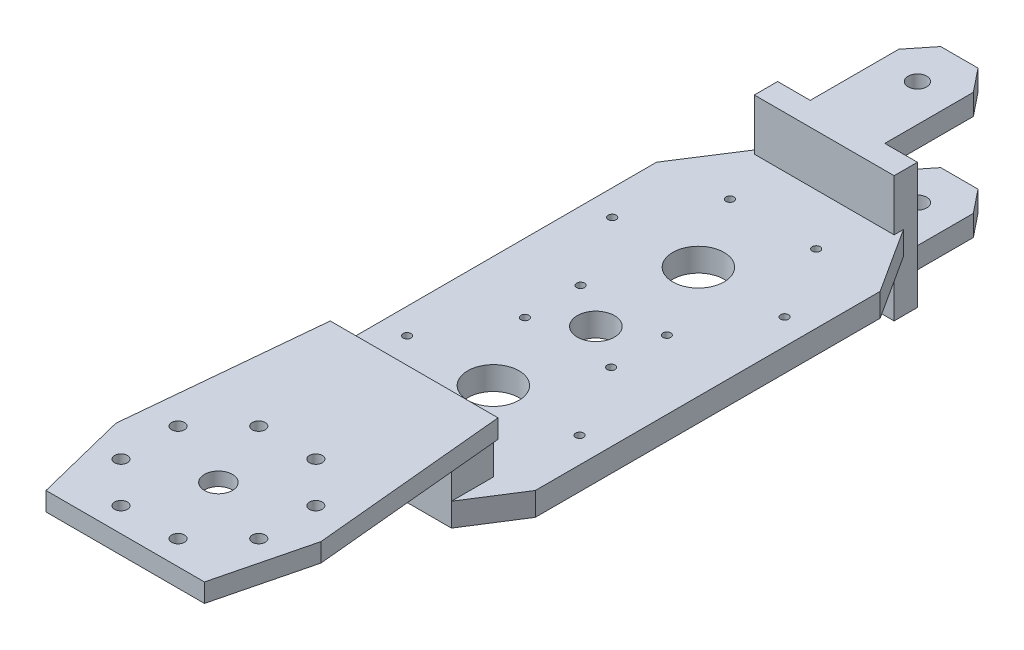
SolidWorks part; units mm, degrees
ref_plane "Front Plane" through (0, 0, 0) normal (0, 0, 1) x (1, 0, 0)
ref_plane "Top Plane" through (0, 0, 0) normal (0, 1, 0) x (1, 0, 0)
ref_plane "Right Plane" through (0, 0, 0) normal (1, 0, 0) x (0, 0, -1)
ref_plane "PL_Knee_Plate_base" through (0, 20, 0) normal (0, 1, 0) x (1, 0, 0)
sketch "SK_Knee_Plate" plane through (0, 20, 0) normal (0, 1, 0) x (1, 0, 0)
  line L0 (-34, -40) -> (34, -40)
  line L1 (34, -40) -> (44, 0)
  line L2 (44, 0) -> (36, 84)
  line L3 (36, 84) -> (-36, 84)
  line L4 (-36, 84) -> (-44, 0)
  line L5 (-44, 0) -> (-34, -40)
  circle A0 centre (29.5641, 12.2459) radius 2.75
  circle A1 centre (12.2459, 29.5641) radius 2.75
  circle A2 centre (-12.2459, 29.5641) radius 2.75
  circle A3 centre (-29.5641, 12.2459) radius 2.75
  circle A4 centre (-29.5641, -12.2459) radius 2.75
  circle A5 centre (-12.2459, -29.5641) radius 2.75
  circle A6 centre (12.2459, -29.5641) radius 2.75
  circle A7 centre (29.5641, -12.2459) radius 2.75
  circle A8 centre (0, 0) radius 6
  dimension "D11_SK_Knee_Plate" = 5.5
  dimension "D14_SK_Knee_Plate" = 5.5
  dimension "D17_SK_Knee_Plate" = 5.5
  dimension "D20_SK_Knee_Plate" = 5.5
  dimension "D23_SK_Knee_Plate" = 5.5
  dimension "D26_SK_Knee_Plate" = 5.5
  dimension "D29_SK_Knee_Plate" = 5.5
  dimension "D32_SK_Knee_Plate" = 5.5
  dimension "D35_SK_Knee_Plate" = 12
  dimension "P1" = 34
  dimension "P2" = 40
  dimension "P3" = 34
  dimension "P4" = 40
  dimension "P5" = 44
  dimension "P6" = 36
  dimension "P7" = 84
  dimension "P8" = 36
  dimension "P9" = 84
  dimension "P10" = 44
  dimension "P12" = 29.5641
  dimension "P13" = 12.2459
  dimension "P15" = 12.2459
  dimension "P16" = 29.5641
  dimension "P18" = 12.2459
  dimension "P19" = 29.5641
  dimension "P21" = 29.5641
  dimension "P22" = 12.2459
  dimension "P24" = 29.5641
  dimension "P25" = 12.2459
  dimension "P27" = 12.2459
  dimension "P28" = 29.5641
  dimension "P30" = 12.2459
  dimension "P31" = 29.5641
  dimension "P33" = 29.5641
  dimension "P34" = 12.2459
extrude "Knee_Plate" add sketch "SK_Knee_Plate" along normal blind 8
ref_plane "PL_Knee_Pilot_Recess_base" through (0, 20, 0) normal (0, 1, 0) x (1, 0, 0)
sketch "SK_Knee_Pilot_Recess" plane through (0, 20, 0) normal (0, 1, 0) x (1, 0, 0)
  circle A0 centre (0, 0) radius 25.15
  dimension "D1_SK_Knee_Pilot_Recess" = 50.3
extrude "Knee_Pilot_Recess" cut sketch "SK_Knee_Pilot_Recess" along normal blind 2.2
ref_plane "PL_Joggle_base" through (0, 0, -84) normal (0, 0, 1) x (1, 0, 0)
sketch "SK_Joggle" plane through (0, 0, -84) normal (0, 0, 1) x (1, 0, 0)
  line L0 (-34, 28) -> (34, 28)
  line L1 (34, 28) -> (34, -5)
  line L2 (34, -5) -> (-34, -5)
  line L3 (-34, -5) -> (-34, 28)
  dimension "P1" = 34
  dimension "P2" = 28
  dimension "P3" = 34
  dimension "P4" = 28
  dimension "P5" = 34
  dimension "P6" = 5
  dimension "P7" = 34
  dimension "P8" = 5
extrude "Joggle" add sketch "SK_Joggle" along normal blind 18
ref_plane "PL_Web_base" through (0, -5, 0) normal (0, 1, 0) x (1, 0, 0)
sketch "SK_Web" plane through (0, -5, 0) normal (0, 1, 0) x (1, 0, 0)
  line L0 (-34, 66) -> (34, 66)
  line L1 (34, 66) -> (48, 88)
  line L2 (48, 88) -> (48, 236)
  line L3 (48, 236) -> (30, 264)
  line L4 (30, 264) -> (-30, 264)
  line L5 (-30, 264) -> (-48, 236)
  line L6 (-48, 236) -> (-48, 88)
  line L7 (-48, 88) -> (-34, 66)
  circle A0 centre (37, 118) radius 1.7
  circle A1 centre (18.5, 150.0429) radius 1.7
  circle A2 centre (-18.5, 150.0429) radius 1.7
  circle A3 centre (-37, 118) radius 1.7
  circle A4 centre (-18.5, 85.9571) radius 1.7
  circle A5 centre (18.5, 85.9571) radius 1.7
  circle A6 centre (37, 206) radius 1.7
  circle A7 centre (18.5, 238.0429) radius 1.7
  circle A8 centre (-18.5, 238.0429) radius 1.7
  circle A9 centre (-37, 206) radius 1.7
  circle A10 centre (-18.5, 173.9571) radius 1.7
  circle A11 centre (18.5, 173.9571) radius 1.7
  circle A12 centre (0, 118) radius 11
  circle A13 centre (0, 206) radius 11
  circle A14 centre (0, 162) radius 8
  dimension "D17_SK_Web" = 3.4
  dimension "D20_SK_Web" = 3.4
  dimension "D23_SK_Web" = 3.4
  dimension "D26_SK_Web" = 3.4
  dimension "D29_SK_Web" = 3.4
  dimension "D32_SK_Web" = 3.4
  dimension "D35_SK_Web" = 3.4
  dimension "D38_SK_Web" = 3.4
  dimension "D41_SK_Web" = 3.4
  dimension "D44_SK_Web" = 3.4
  dimension "D47_SK_Web" = 3.4
  dimension "D50_SK_Web" = 3.4
  dimension "D53_SK_Web" = 22
  dimension "D55_SK_Web" = 22
  dimension "D57_SK_Web" = 16
  dimension "P1" = 34
  dimension "P2" = 66
  dimension "P3" = 34
  dimension "P4" = 66
  dimension "P5" = 48
  dimension "P6" = 88
  dimension "P7" = 48
  dimension "P8" = 236
  dimension "P9" = 30
  dimension "P10" = 264
  dimension "P11" = 30
  dimension "P12" = 264
  dimension "P13" = 48
  dimension "P14" = 236
  dimension "P15" = 48
  dimension "P16" = 88
  dimension "P18" = 37
  dimension "P19" = 118
  dimension "P21" = 18.5
  dimension "P22" = 150.0429
  dimension "P24" = 18.5
  dimension "P25" = 150.0429
  dimension "P27" = 37
  dimension "P28" = 118
  dimension "P30" = 18.5
  dimension "P31" = 85.9571
  dimension "P33" = 18.5
  dimension "P34" = 85.9571
  dimension "P36" = 37
  dimension "P37" = 206
  dimension "P39" = 18.5
  dimension "P40" = 238.0429
  dimension "P42" = 18.5
  dimension "P43" = 238.0429
  dimension "P45" = 37
  dimension "P46" = 206
  dimension "P48" = 18.5
  dimension "P49" = 173.9571
  dimension "P51" = 18.5
  dimension "P52" = 173.9571
  dimension "P54" = 118
  dimension "P56" = 206
  dimension "P58" = 162
extrude "Web" add sketch "SK_Web" along normal blind 10
ref_plane "PL_Fork_Bar_base" through (0, 0, -270) normal (0, 0, 1) x (1, 0, 0)
sketch "SK_Fork_Bar" plane through (0, 0, -270) normal (0, 0, 1) x (1, 0, 0)
  line L0 (-30, 27) -> (30, 27)
  line L1 (30, 27) -> (30, -27)
  line L2 (30, -27) -> (-30, -27)
  line L3 (-30, -27) -> (-30, 27)
  dimension "P1" = 30
  dimension "P2" = 27
  dimension "P3" = 30
  dimension "P4" = 27
  dimension "P5" = 30
  dimension "P6" = 27
  dimension "P7" = 30
  dimension "P8" = 27
extrude "Fork_Bar" add sketch "SK_Fork_Bar" along normal blind 10
ref_plane "PL_Tine_Lat_base" through (0, -27, 0) normal (0, 1, 0) x (1, 0, 0)
sketch "SK_Tine_Lat" plane through (0, -27, 0) normal (0, 1, 0) x (1, 0, 0)
  line L0 (-16, 260) -> (16, 260)
  line L1 (16, 260) -> (16, 308)
  line L2 (16, 308) -> (8, 318)
  line L3 (8, 318) -> (-8, 318)
  line L4 (-8, 318) -> (-16, 308)
  line L5 (-16, 308) -> (-16, 260)
  circle A0 centre (0, 300) radius 4
  dimension "D13_SK_Tine_Lat" = 8
  dimension "P1" = 16
  dimension "P2" = 260
  dimension "P3" = 16
  dimension "P4" = 260
  dimension "P5" = 16
  dimension "P6" = 308
  dimension "P7" = 8
  dimension "P8" = 318
  dimension "P9" = 8
  dimension "P10" = 318
  dimension "P11" = 16
  dimension "P12" = 308
  dimension "P14" = 300
extrude "Tine_Lat" add sketch "SK_Tine_Lat" along normal blind 9
ref_plane "PL_Tine_Med_base" through (0, 18, 0) normal (0, 1, 0) x (1, 0, 0)
sketch "SK_Tine_Med" plane through (0, 18, 0) normal (0, 1, 0) x (1, 0, 0)
  line L0 (-16, 260) -> (16, 260)
  line L1 (16, 260) -> (16, 308)
  line L2 (16, 308) -> (8, 318)
  line L3 (8, 318) -> (-8, 318)
  line L4 (-8, 318) -> (-16, 308)
  line L5 (-16, 308) -> (-16, 260)
  circle A0 centre (0, 300) radius 4
  dimension "D13_SK_Tine_Med" = 8
  dimension "P1" = 16
  dimension "P2" = 260
  dimension "P3" = 16
  dimension "P4" = 260
  dimension "P5" = 16
  dimension "P6" = 308
  dimension "P7" = 8
  dimension "P8" = 318
  dimension "P9" = 8
  dimension "P10" = 318
  dimension "P11" = 16
  dimension "P12" = 308
  dimension "P14" = 300
extrude "Tine_Med" add sketch "SK_Tine_Med" along normal blind 9
ref_plane "PL_AnkleZ" through (0, 0, -300) normal (0, 0, 1) x (1, 0, 0)
ref_axis "AX_AnklePitch" through (0, 30.75, -300) along (0, -1, 0)
ref_axis "AX_KneeY" through (0, 30.75, 0) along (0, -1, 0)
ref_plane "PL_KneeRef" through (0, 0, 0) normal (-0.9239, 0, 0.3827) x (0, -1, 0)
equation "\"Shin_length\" = 300"
equation "\"AnkleA_z\" = -118"
equation "\"AnkleB_z\" = -206"
